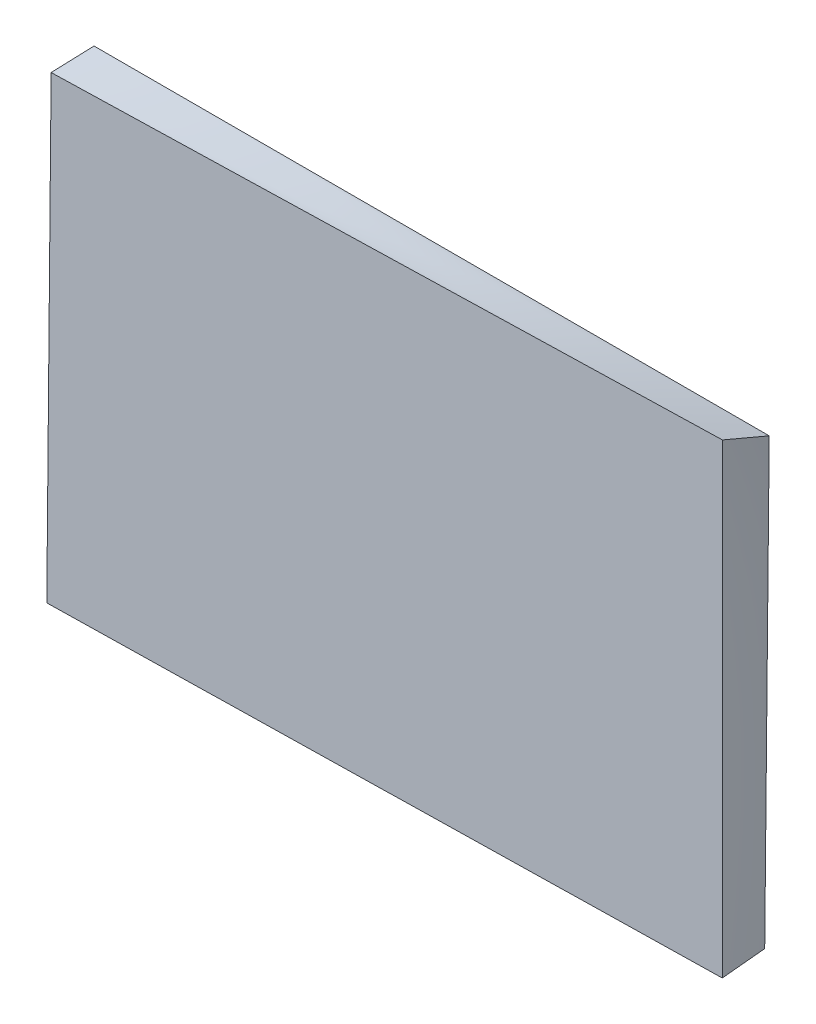
SolidWorks part; units mm, degrees
ref_plane "Ebene vorne" through (0, 0, 0) normal (0, 0, 1) x (1, 0, 0)
ref_plane "Ebene oben" through (0, 0, 0) normal (0, 1, 0) x (1, 0, 0)
ref_plane "Ebene rechts" through (0, 0, 0) normal (1, 0, 0) x (0, 0, -1)
other "Massenmittelpunkt"
sketch "Skizze1" plane through (0, 0, 0) normal (0, 0, 1) x (1, 0, 0)
  line L0 (-14.9998, 9.9997) -> (-14.9998, -10.1003)
  line L1 (-14.9998, -10.1003) -> (14.8995, -9.8992)
  line L2 (14.8995, -9.8992) -> (15.1002, 9.9997)
  line L3 (15.1002, 9.9997) -> (-14.9998, 9.9997)
  line L4 (-14.9998, -0.0503) -> (14.9998, 0.0503) construction
  line L5 (0.0502, 9.9997) -> (-0.0502, -9.9997) construction
  point P3 (0.0502, 9.9997)
  point P5 (14.9998, 0.0503)
  point P6 (-0.0502, -9.9997)
  point P7 (-14.9998, -0.0503)
  point P12 (0, 0)
  dimension "D1" = 30.1
  dimension "D2" = 29.9
  dimension "D3" = 20.1
  dimension "D4" = 19.9
  dimension "D5" = 90
ref_axis "Achse1" through (11, 0, 0) along (-1, 0, 0)
ref_plane "Rotation_Plane" through (0, 0, 0) normal (0, -0.0349, -0.9994) x (-1, 0, 0)
ref_plane "Top_Plane" through (0, 0.0698, 1.9988) normal (0, -0.0349, -0.9994) x (-1, 0, 0)
sketch "Skizze2" plane through (0, 0.0698, 1.9988) normal (0, -0.0349, -0.9994) x (-1, 0, 0)
  line L0 (15.2488, 9.6195) -> (14.7486, -10.2742)
  line L1 (14.7486, -10.2742) -> (-15.3462, -9.7166)
  line L2 (-15.3462, -9.7166) -> (-14.6512, 10.3713)
  line L3 (-14.6512, 10.3713) -> (15.2488, 9.6195)
  line L4 (0.2988, 9.9954) -> (-0.2988, -9.9954) construction
  line L5 (14.9987, -0.3273) -> (-14.9987, 0.3273) construction
  line L6 (-0.0502, 9.9937) -> (0.0502, -9.9937) construction
  line L7 (-0.0502, 9.9937) -> (0.0502, -9.9937) construction
  point P0 (0, 0)
  point P6 (0.2988, 9.9954)
  point P7 (-14.9987, 0.3273)
  point P8 (-0.2988, -9.9954)
  point P9 (14.9987, -0.3273)
  point P14 (0, 0)
  dimension "D5" = 90
  dimension "D1" = 19.9
  dimension "D2" = 20.1
  dimension "D3" = 29.9
  dimension "D4" = 30.1
  dimension "D6" = 2
loft "Ausformung2" add profiles "Skizze1", "Skizze2" connector at (-14.9998, -10.1003, 0) connector at (-14.7486, -10.1981, 2.3573)
ref_point "SWASI_Vision_Point_1_T"
ref_point "SWASI_Vision_Point_1_B"
ref_point "SWASI_Vision_Point_2_T"
ref_point "SWASI_Vision_Point_2_B"
ref_point "SWASI_Vision_Point_3_T"
ref_point "SWASI_Vision_Point_3_B"
ref_point "SWASI_Vision_Point_4_T"
ref_point "SWASI_Vision_Point_4_B"
sketch "Skizze3" plane through (0, 0.0698, 1.9988) normal (0, 0.0349, 0.9994) x (1, 0, 0)
  line L0 (-14.9987, -0.3273) -> (14.9987, 0.3273) construction
  line L1 (-0.2988, 9.9954) -> (0.2988, -9.9954) construction
  line L3 (-14, -9) -> (14, -9)
  line L4 (14.6512, 10.3713) -> (-15.2488, 9.6195)
  line L5 (-15.2488, 9.6195) -> (-14.7486, -10.2742)
  line L6 (-14.7486, -10.2742) -> (15.3462, -9.7166)
  line L7 (15.3462, -9.7166) -> (14.6512, 10.3713)
  line L8 (14.6512, 10.3713) -> (-15.2488, 9.6195) construction
  line L9 (-15.2488, 9.6195) -> (-14.7486, -10.2742) construction
  line L10 (-14.7486, -10.2742) -> (15.3462, -9.7166) construction
  line L11 (15.3462, -9.7166) -> (14.6512, 10.3713) construction
  line L12 (-14, -9) -> (-14, 9)
  line L13 (-14, 9) -> (14, 9)
  line L14 (14, -9) -> (14, 9)
  line L15 (-14, -9) -> (14, 9) construction
  line L16 (-14, 9) -> (14, -9) construction
  point P8 (0, 0)
  point P9 (0, 0)
  dimension "D2" = 28
  dimension "D3" = 18
  dimension "D1" = 0
ref_point "SWASI_Laser_1_T"
ref_point "SWASI_Laser_2_T"
ref_point "SWASI_Laser_3_T"
ref_point "SWASI_Laser_4_T"
ref_point "SWASI_Gripping_Point"
sketch "Skizze4" plane through (0, 0, 0) normal (0, 0, -1) x (-1, 0, 0)
  line L1 (14, 9) -> (-14, 9)
  line L2 (14, 9) -> (14, -9)
  line L3 (14, -9) -> (-14, -9)
  line L4 (-14, 9) -> (-14, -9)
  line L5 (14, 9) -> (-14, -9) construction
  line L6 (14, -9) -> (-14, 9) construction
  point P0 (0, 0)
  point P2 (0, 0)
  dimension "D1" = 28
  dimension "D2" = 18
ref_point "SWASI_Laser_1_B"
ref_point "SWASI_Laser_2_B"
ref_point "SWASI_Laser_3_B"
ref_point "SWASI_Laser_4_B"
ref_plane "SWASI_Top_Plane" through (0, 0.0698, 1.9988) normal (0, -0.0349, -0.9994) x (-1, 0, 0)
ref_plane "SWASI_Bottom_Plane" through (0, 0, 0) normal (0, 0, -1) x (-1, 0, 0)
ref_axis "SWASI_Bottom_Axis" through (14.8995, -9.8992, 0) along (-1, -0.0067, 0)
ref_axis "SWASI_Top_Axis" through (15.3462, -9.6409, 2.3379) along (-0.9998, -0.0185, 0.0006)
sketch "Axis_Center_B" plane through (0, 0, 0) normal (0, 0, -1) x (-1, 0, 0)
  line L0 (14.9998, -10.1003) -> (-14.8995, -9.8992) construction
  line L1 (14.9998, -10.1003) -> (-14.8995, -9.8992)
  point P2 (0.0502, -9.9997)
sketch "Skizze6" plane through (0, 0.0698, 1.9988) normal (0, 0.0349, 0.9994) x (1, 0, 0)
  line L0 (15.3462, -9.7166) -> (-14.7486, -10.2742) construction
  point P0 (0.2988, -9.9954)
  point P1 (-12.736, 25.2765)
ref_point "SWASI_Axis_Center_B"
ref_point "SWASI_Axis_Center_T"
ref_plane "SWASI_Axis_T_Plane" through (0.2988, -9.9195, 2.3476) normal (-0.9998, -0.0185, 0.0006) x (0.0006, 0, 1)
ref_plane "SWASI_Axis_B_Plane" through (-0.0502, -9.9997, 0) normal (-1, -0.0067, 0) x (0, 0, 1)
ref_plane "Bottom_Reference" through (0, 0, 3) normal (0, 0, -1) x (-1, 0, 0)
ref_plane "Top_Reference" through (0, -0.0349, -0.9994) normal (0, 0.0349, 0.9994) x (1, 0, 0)
sketch "Skizze7" plane through (0, 229.1773, 3) normal (0, 0, -1) x (1, 0, 0)
  point P0 (-14.9998, 239.2776)
ref_point "SWASI_Front_Bottom_Reference"
ref_plane "SWASI_Front_Plane_B" through (0.0672, -9.999, 0) normal (-0.0067, 1, 0) x (1, 0.0067, 0.0001)
sketch "Skizze9" plane through (0, 229.0028, -8.9976) normal (0, 0.0349, 0.9994) x (-1, 0, 0)
  point P0 (-15.3462, 238.8939)
ref_point "SWASI_Front_Top_Reference"
ref_plane "SWASI_Front_Plane_T" through (0.1852, -9.9914, 0.3489) normal (0.0185, -0.9992, 0.0349) x (-0.9998, -0.0185, 0)
sketch "Skizze10" plane through (0, 0, 0) normal (0, 0, -1) x (-1, 0, 0)
  line L0 (-16.8995, 11.9997) -> (-16.8995, -8.0003) construction
  line L1 (-16.8995, 11.9997) -> (3.1005, 11.9997) construction
  point P2 (-14.8995, -9.8992)
  point P4 (14.9998, 9.9997)
  dimension "D1" = 20
  dimension "D2" = 20
  dimension "D3" = 2
  dimension "D4" = 2
ref_point "Punkt44"
equation "\"Length_1\"= 20.1"
equation "\"Length_2\"= 19.9"
equation "\"Length_3\"= 30.1"
equation "\"Length_4\"= 29.9"
equation "\"D1@Skizze1\"=\"Length_3\""
equation "\"D2@Skizze1\"=\"Length_4\""
equation "\"D3@Skizze1\"=\"Length_1\""
equation "\"D4@Skizze1\"=\"Length_2\""
equation "\"Angle_1\"= 90"
equation "\"Angle_2\"= 90"
equation "\"Plane_Angle\"= 1"
equation "\"D5@Skizze1\"=\"Angle_1\""
equation "\"Plane_Distance\"= 1"
equation "\"Length_1_1\"= 19.9"
equation "\"Length_1_2\"= 20.1"
equation "\"Length_1_3\"= 29.9"
equation "\"Length_1_4\"= 30.1"
equation "\"Angle_3\"= 90"
equation "\"Angle_4\"= 90"
equation "\"D1@Skizze2\"=\"Length_1_1\""
equation "\"D2@Skizze2\"=\"Length_1_2\""
equation "\"D3@Skizze2\"=\"Length_1_3\""
equation "\"D4@Skizze2\"=\"Length_1_4\""
equation "\"D5@Skizze2\"=\"Angle_3\""
equation "\"Angle_Plane_rot\"= 2"
equation "\"D6@Skizze2\"=\"Angle_Plane_rot\""
